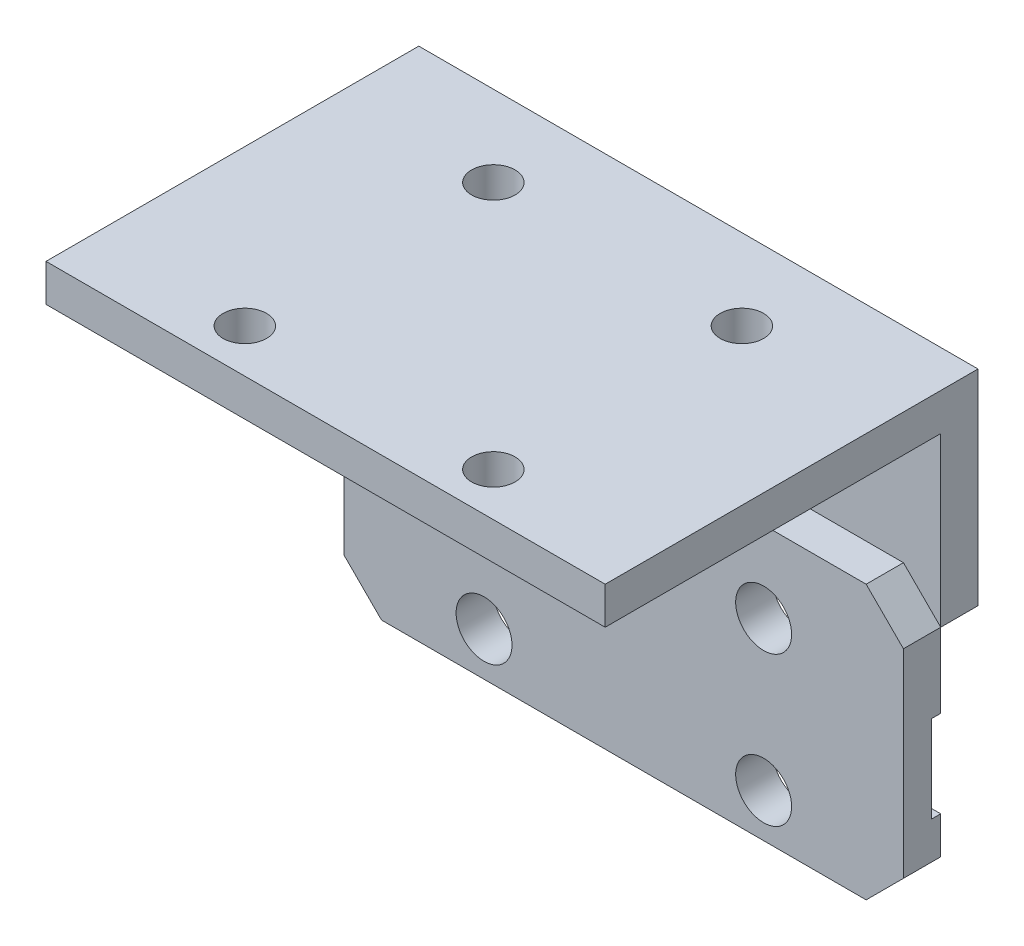
SolidWorks part; units mm, degrees
ref_plane "Front Plane" through (0, 0, 0) normal (0, 0, 1) x (1, 0, 0)
ref_plane "Top Plane" through (0, 0, 0) normal (0, 1, 0) x (1, 0, 0)
ref_plane "Right Plane" through (0, 0, 0) normal (1, 0, 0) x (0, 0, -1)
sketch "Sketch1" plane through (0, 0, 0) normal (0, 1, 0) x (1, 0, 0)
  line L1 (-22.5, -13.5) -> (22.5, -13.5)
  line L2 (-22.5, -13.5) -> (-22.5, 13.5)
  line L3 (-22.5, 13.5) -> (22.5, 13.5)
  line L4 (22.5, -13.5) -> (22.5, 13.5)
  line L5 (-22.5, -13.5) -> (22.5, 13.5) construction
  line L6 (-22.5, 13.5) -> (22.5, -13.5) construction
  point P0 (0, 0)
  dimension "D1" = 45
  dimension "D2" = 27
extrude "Boss-Extrude1" add sketch "Sketch1" along normal blind 3
sketch "Sketch2" plane through (0, 3, 0) normal (0, 1, 0) x (1, 0, 0)
  line L0 (0, 13.5) -> (0, -13.5) construction
  line L1 (22.5, 13.5) -> (-22.5, 13.5) construction
  line L2 (-22.5, -13.5) -> (22.5, -13.5) construction
  line L3 (-22.5, 0) -> (22.5, 0) construction
  line L4 (-22.5, 13.5) -> (-22.5, -13.5) construction
  line L5 (22.5, -13.5) -> (22.5, 13.5) construction
  circle A0 centre (-10, 10) radius 1.75
  circle A1 centre (10, 10) radius 1.75
  circle A2 centre (10, -10) radius 1.75
  circle A3 centre (-10, -10) radius 1.75
  dimension "D1" = 3.5
  dimension "D2" = 10
  dimension "D3" = 10
extrude "Cut-Extrude1" cut sketch "Sketch2" against normal up to next
sketch "Sketch3" plane through (0, 0, -13.5) normal (0, 0, -1) x (-1, 0, 0)
  line L0 (-22.5, 0) -> (-22.5, -32.5) construction
  line L1 (22.5, 3) -> (-22.5, 3)
  line L2 (22.5, 3) -> (22.5, -32.5)
  line L3 (22.5, -32.5) -> (-22.5, -32.5)
  line L4 (-22.5, 3) -> (-22.5, -32.5)
  point P8 (-22.5, -29.6181)
  dimension "D1" = 32.5
extrude "Boss-Extrude2" add sketch "Sketch3" along normal blind 3
sketch "Sketch4" plane through (0, 0, -13.5) normal (0, 0, 1) x (1, 0, 0)
  line L0 (-22.5, -32.5) -> (-22.5, 0) construction
  line L1 (22.5, -32.5) -> (-22.5, -32.5)
  line L2 (22.5, -32.5) -> (22.5, -10.5)
  line L3 (22.5, -10.5) -> (-22.5, -10.5)
  line L4 (-22.5, -32.5) -> (-22.5, -10.5)
  line L5 (-22.5, 0) -> (22.5, 0) construction
  dimension "D1" = 10.5
extrude "Boss-Extrude3" add sketch "Sketch4" along normal blind 3
sketch "Sketch6" plane through (0, 0, -16.5) normal (0, 0, -1) x (-1, 0, 0)
  line L0 (0, -32.5) -> (0, 3) construction
  line L1 (-22.5, -32.5) -> (22.5, -32.5) construction
  line L2 (22.5, 3) -> (-22.5, 3) construction
  line L4 (22.5, -13.5) -> (-22.5, -13.5)
  line L5 (22.5, -13.5) -> (22.5, -32.5)
  line L6 (22.5, -32.5) -> (-22.5, -32.5)
  line L7 (-22.5, -13.5) -> (-22.5, -32.5)
  line L8 (22.5, -13.5) -> (-22.5, -32.5) construction
  line L9 (22.5, -32.5) -> (-22.5, -13.5) construction
  point P6 (0, -23)
  dimension "D1" = 9.5
extrude "Cut-Extrude2" cut sketch "Sketch6" against normal blind 3
sketch "Sketch7" plane through (0, 0, -13.5) normal (0, 0, -1) x (-1, 0, 0)
  line L0 (22.5, -23) -> (-22.5, -23) construction
  line L1 (22.5, -32.5) -> (22.5, -13.5) construction
  line L2 (-22.5, -13.5) -> (-22.5, -32.5) construction
  line L3 (19.5, -19.5) -> (19.5, -26.5)
  line L4 (21.5, -19.5) -> (20.5, -19.5)
  line L5 (21.5, -19.5) -> (21.5, -26.5)
  line L6 (21.5, -26.5) -> (20.5, -26.5)
  line L7 (20.5, -19.5) -> (20.5, -26.5)
  line L8 (21.5, -19.5) -> (20.5, -26.5) construction
  line L9 (21.5, -26.5) -> (20.5, -19.5) construction
  line L10 (19.5, -19.5) -> (18.5, -19.5)
  line L11 (18.5, -19.5) -> (18.5, -26.5)
  line L12 (19.5, -26.5) -> (18.5, -26.5)
  line L13 (17.5, -19.5) -> (17.5, -26.5)
  line L14 (17.5, -19.5) -> (16.5, -19.5)
  line L15 (16.5, -19.5) -> (16.5, -26.5)
  line L16 (17.5, -26.5) -> (16.5, -26.5)
  line L17 (15.5, -19.5) -> (15.5, -26.5)
  line L18 (15.5, -19.5) -> (14.5, -19.5)
  line L19 (14.5, -19.5) -> (14.5, -26.5)
  line L20 (15.5, -26.5) -> (14.5, -26.5)
  line L21 (13.5, -19.5) -> (13.5, -26.5)
  line L22 (13.5, -19.5) -> (12.5, -19.5)
  line L23 (12.5, -19.5) -> (12.5, -26.5)
  line L24 (13.5, -26.5) -> (12.5, -26.5)
  line L25 (11.5, -19.5) -> (11.5, -26.5)
  line L26 (11.5, -19.5) -> (10.5, -19.5)
  line L27 (10.5, -19.5) -> (10.5, -26.5)
  line L28 (11.5, -26.5) -> (10.5, -26.5)
  line L29 (9.5, -19.5) -> (9.5, -26.5)
  line L30 (9.5, -19.5) -> (8.5, -19.5)
  line L31 (8.5, -19.5) -> (8.5, -26.5)
  line L32 (9.5, -26.5) -> (8.5, -26.5)
  line L33 (7.5, -19.5) -> (7.5, -26.5)
  line L34 (7.5, -19.5) -> (6.5, -19.5)
  line L35 (6.5, -19.5) -> (6.5, -26.5)
  line L36 (7.5, -26.5) -> (6.5, -26.5)
  line L37 (5.5, -19.5) -> (5.5, -26.5)
  line L38 (5.5, -19.5) -> (4.5, -19.5)
  line L39 (4.5, -19.5) -> (4.5, -26.5)
  line L40 (5.5, -26.5) -> (4.5, -26.5)
  line L41 (3.5, -19.5) -> (3.5, -26.5)
  line L42 (3.5, -19.5) -> (2.5, -19.5)
  line L43 (2.5, -19.5) -> (2.5, -26.5)
  line L44 (3.5, -26.5) -> (2.5, -26.5)
  line L45 (1.5, -19.5) -> (1.5, -26.5)
  line L46 (1.5, -19.5) -> (0.5, -19.5)
  line L47 (0.5, -19.5) -> (0.5, -26.5)
  line L48 (1.5, -26.5) -> (0.5, -26.5)
  line L49 (-0.5, -19.5) -> (-0.5, -26.5)
  line L50 (-0.5, -19.5) -> (-1.5, -19.5)
  line L51 (-1.5, -19.5) -> (-1.5, -26.5)
  line L52 (-0.5, -26.5) -> (-1.5, -26.5)
  line L53 (-2.5, -19.5) -> (-2.5, -26.5)
  line L54 (-2.5, -19.5) -> (-3.5, -19.5)
  line L55 (-3.5, -19.5) -> (-3.5, -26.5)
  line L56 (-2.5, -26.5) -> (-3.5, -26.5)
  line L57 (-4.5, -19.5) -> (-4.5, -26.5)
  line L58 (-4.5, -19.5) -> (-5.5, -19.5)
  line L59 (-5.5, -19.5) -> (-5.5, -26.5)
  line L60 (-4.5, -26.5) -> (-5.5, -26.5)
  line L61 (-6.5, -19.5) -> (-6.5, -26.5)
  line L62 (-6.5, -19.5) -> (-7.5, -19.5)
  line L63 (-7.5, -19.5) -> (-7.5, -26.5)
  line L64 (-6.5, -26.5) -> (-7.5, -26.5)
  line L65 (-8.5, -19.5) -> (-8.5, -26.5)
  line L66 (-8.5, -19.5) -> (-9.5, -19.5)
  line L67 (-9.5, -19.5) -> (-9.5, -26.5)
  line L68 (-8.5, -26.5) -> (-9.5, -26.5)
  line L69 (-10.5, -19.5) -> (-10.5, -26.5)
  line L70 (-10.5, -19.5) -> (-11.5, -19.5)
  line L71 (-11.5, -19.5) -> (-11.5, -26.5)
  line L72 (-10.5, -26.5) -> (-11.5, -26.5)
  line L73 (-12.5, -19.5) -> (-12.5, -26.5)
  line L74 (-12.5, -19.5) -> (-13.5, -19.5)
  line L75 (-13.5, -19.5) -> (-13.5, -26.5)
  line L76 (-12.5, -26.5) -> (-13.5, -26.5)
  line L77 (-14.5, -19.5) -> (-14.5, -26.5)
  line L78 (-14.5, -19.5) -> (-15.5, -19.5)
  line L79 (-15.5, -19.5) -> (-15.5, -26.5)
  line L80 (-14.5, -26.5) -> (-15.5, -26.5)
  line L81 (-16.5, -19.5) -> (-16.5, -26.5)
  line L82 (-16.5, -19.5) -> (-17.5, -19.5)
  line L83 (-17.5, -19.5) -> (-17.5, -26.5)
  line L84 (-16.5, -26.5) -> (-17.5, -26.5)
  line L85 (-18.5, -19.5) -> (-18.5, -26.5)
  line L86 (-18.5, -19.5) -> (-19.5, -19.5)
  line L87 (-19.5, -19.5) -> (-19.5, -26.5)
  line L88 (-18.5, -26.5) -> (-19.5, -26.5)
  line L89 (-20.5, -19.5) -> (-20.5, -26.5)
  line L90 (-20.5, -19.5) -> (-21.5, -19.5)
  line L91 (-21.5, -19.5) -> (-21.5, -26.5)
  line L92 (-20.5, -26.5) -> (-21.5, -26.5)
  point P6 (21, -23)
  dimension "D1" = 7
  dimension "D2" = 1
  dimension "D3" = 1
  dimension "D5" = 2
  dimension "D4" = 22
extrude "Cut-Extrude3" cut sketch "Sketch7" against normal blind 1.5
sketch "Sketch8" plane through (0, 0, -13.5) normal (0, 0, -1) x (-1, 0, 0)
  line L0 (0, -13.5) -> (0, -32.5) construction
  line L1 (22.5, -13.5) -> (-22.5, -13.5) construction
  line L2 (-22.5, -32.5) -> (22.5, -32.5) construction
  line L3 (-22.5, -13.5) -> (-22.5, -32.5) construction
  line L4 (22.5, -19.5) -> (-22.5, -19.5)
  line L5 (22.5, -19.5) -> (22.5, -26.5)
  line L6 (22.5, -26.5) -> (-22.5, -26.5)
  line L7 (-22.5, -19.5) -> (-22.5, -26.5)
  line L8 (22.5, -19.5) -> (-22.5, -26.5) construction
  line L9 (22.5, -26.5) -> (-22.5, -19.5) construction
  point P6 (0, -23)
  dimension "D1" = 7
extrude "Cut-Extrude4" cut sketch "Sketch8" against normal blind 0.75
sketch "Sketch10" plane through (0, 0, -13.5) normal (0, 0, -1) x (-1, 0, 0)
  line L0 (0, -32.5) -> (0, -13.5) construction
  line L1 (-22.5, -32.5) -> (22.5, -32.5) construction
  line L2 (22.5, -13.5) -> (-22.5, -13.5) construction
  line L3 (0, -23) -> (22.5, -23) construction
  line L4 (22.5, -26.5) -> (22.5, -19.5) construction
  line L5 (11.25, -23) -> (11.25, -32.5) construction
  circle A1 centre (11.25, -29) radius 2.25
  circle A2 centre (11.25, -17) radius 2.25
  circle A3 centre (-11.25, -17) radius 2.25
  circle A4 centre (-11.25, -29) radius 2.25
  dimension "D1" = 3.5
  dimension "D2" = 4.5
extrude "Cut-Extrude5" cut sketch "Sketch10" against normal up to next and the other way through all
chamfer "Chamfer1" distance 3 angle 45 4 edges at (-22.5, -10.5, -12) (22.5, -10.5, -12) (22.5, -32.5, -12) (-22.5, -32.5, -12)
